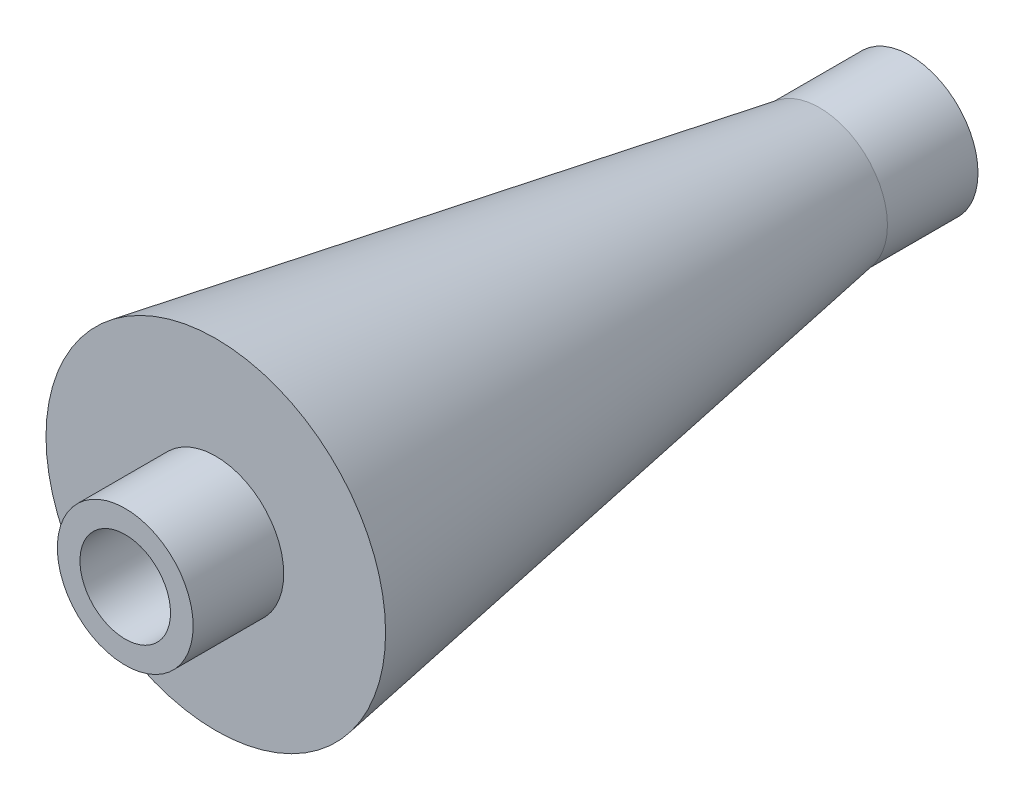
SolidWorks part; units mm, degrees
ref_plane "Front Plane" through (0, 0, 0) normal (0, 0, 1) x (1, 0, 0)
ref_plane "Top Plane" through (0, 0, 0) normal (0, 1, 0) x (1, 0, 0)
ref_plane "Right Plane" through (0, 0, 0) normal (1, 0, 0) x (0, 0, -1)
sketch "Sketch1" plane through (0, 0, 0) normal (0, 1, 0) x (1, 0, 0)
  line L0 (7.1438, 19.05) -> (7.1438, 9.525) construction
  line L1 (7.1438, 9.525) -> (-7.1438, 9.525) construction
  line L2 (17.8594, 19.05) -> (-17.8594, 19.05) construction
  line L3 (7.1437, 92.075) -> (-7.1437, 92.075) construction
  line L4 (7.1438, 82.55) -> (7.1437, 92.075) construction
  line L5 (7.1438, 82.55) -> (17.8594, 19.05) construction
  line L7 (7.1438, 19.05) -> (7.1438, 9.525)
  line L8 (7.1438, 9.525) -> (4.7625, 9.525)
  line L9 (17.8594, 19.05) -> (7.1438, 19.05)
  line L10 (7.1437, 92.075) -> (4.7625, 92.075)
  line L11 (7.1438, 82.55) -> (7.1437, 92.075)
  line L12 (7.1438, 82.55) -> (17.8594, 19.05)
  line L14 (4.7625, -1.5875) -> (4.7625, 104.775) construction
  line L15 (4.7625, 9.525) -> (4.7625, 92.075)
  line L16 (0, -1.5875) -> (0, 104.775) construction
  line L17 (0, -1.5875) -> (0, 104.775)
revolve "Revolve1" add sketch "Sketch1" angle 360 about L17 region at (8.9716, 0, -44.0923)
